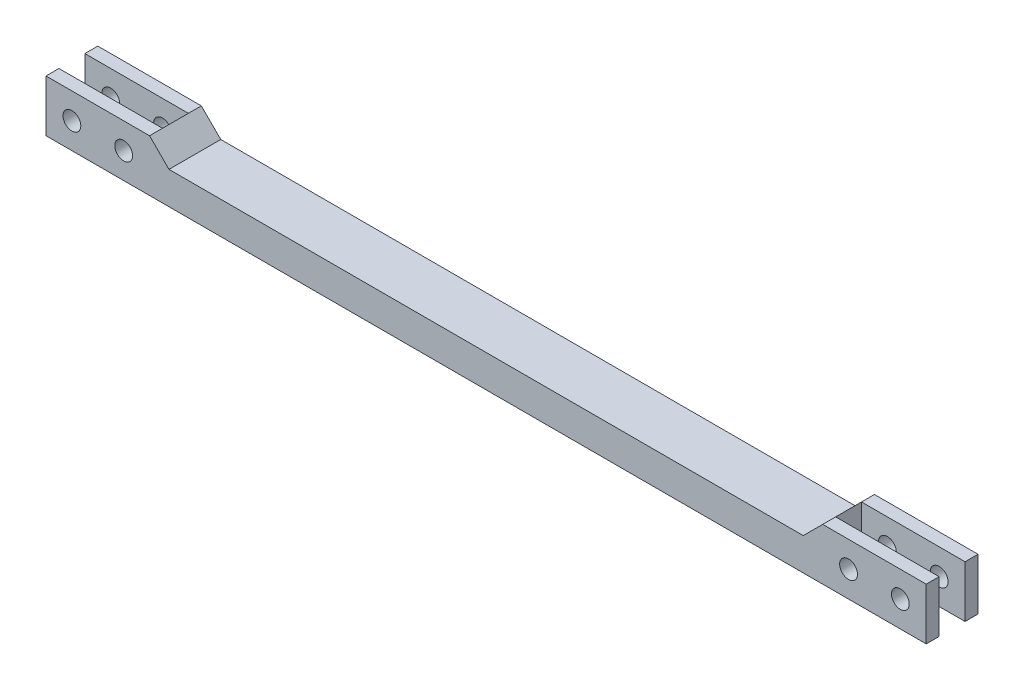
SolidWorks part; units mm, degrees
ref_plane "Front Plane" through (0, 0, 0) normal (0, 0, 1) x (1, 0, 0)
ref_plane "Top Plane" through (0, 0, 0) normal (0, 1, 0) x (1, 0, 0)
ref_plane "Right Plane" through (0, 0, 0) normal (1, 0, 0) x (0, 0, -1)
sketch "Sketch1" plane through (0, 0, 0) normal (0, 1, 0) x (1, 0, 0)
  line L0 (-107.95, 0) -> (107.95, 0)
  line L1 (107.95, 0) -> (107.95, 3.175)
  line L2 (107.95, 3.175) -> (82.55, 3.175)
  line L3 (82.55, 3.175) -> (82.55, 9.525)
  line L4 (82.55, 9.525) -> (107.95, 9.525)
  line L5 (107.95, 9.525) -> (107.95, 12.7)
  line L6 (107.95, 12.7) -> (-107.95, 12.7)
  line L7 (-107.95, 12.7) -> (-107.95, 9.525)
  line L8 (-107.95, 9.525) -> (-82.55, 9.525)
  line L9 (-82.55, 9.525) -> (-82.55, 3.175)
  line L10 (-82.55, 3.175) -> (-107.95, 3.175)
  line L11 (-107.95, 3.175) -> (-107.95, 0)
  point P4 (0, 0)
  dimension "D1" = 215.9
  dimension "D2" = 12.7
  dimension "D3" = 3.175
  dimension "D4" = 3.175
  dimension "D5" = 25.4
  dimension "D6" = 25.4
extrude "Boss-Extrude1" add sketch "Sketch1" along normal mid plane 12.7
sketch "Sketch2" plane through (0, 0, 0) normal (0, 0, 1) x (1, 0, 0)
  line L0 (-107.95, 6.35) -> (-107.95, -6.35) construction
  line L1 (107.95, 6.35) -> (107.95, -6.35) construction
  circle A0 centre (-101.6, 0) radius 2.1828
  circle A1 centre (-88.9, 0) radius 2.1828
  circle A2 centre (101.6, 0) radius 2.1828
  circle A3 centre (88.9, 0) radius 2.1828
  dimension "D5" = 4.3656
  dimension "D6" = 4.3656
  dimension "D7" = 4.3656
  dimension "D8" = 4.3656
  dimension "D1" = 6.35
  dimension "D2" = 12.7
  dimension "D3" = 6.35
  dimension "D4" = 12.7
extrude "Cut-Extrude1" cut sketch "Sketch2" against normal through all both and the other way through all
sketch "Sketch3" plane through (0, 0, 0) normal (0, 0, 1) x (1, 0, 0)
  line L0 (-82.55, 6.35) -> (-77.7875, 1.5875)
  line L1 (-107.95, 6.35) -> (107.95, 6.35) construction
  line L2 (-77.7875, 1.5875) -> (77.7875, 1.5875)
  line L3 (77.7875, 1.5875) -> (82.55, 6.35)
  line L4 (-107.95, 6.35) -> (-107.95, -6.35) construction
  line L5 (107.95, 6.35) -> (107.95, -6.35) construction
  line L6 (-82.55, 6.35) -> (82.55, 6.35)
  dimension "D1" = 25.4
  dimension "D2" = 25.4
  dimension "D3" = 4.7625
  dimension "D4" = 45
  dimension "D5" = 45
extrude "Cut-Extrude2" cut sketch "Sketch3" against normal through all both and the other way through all
